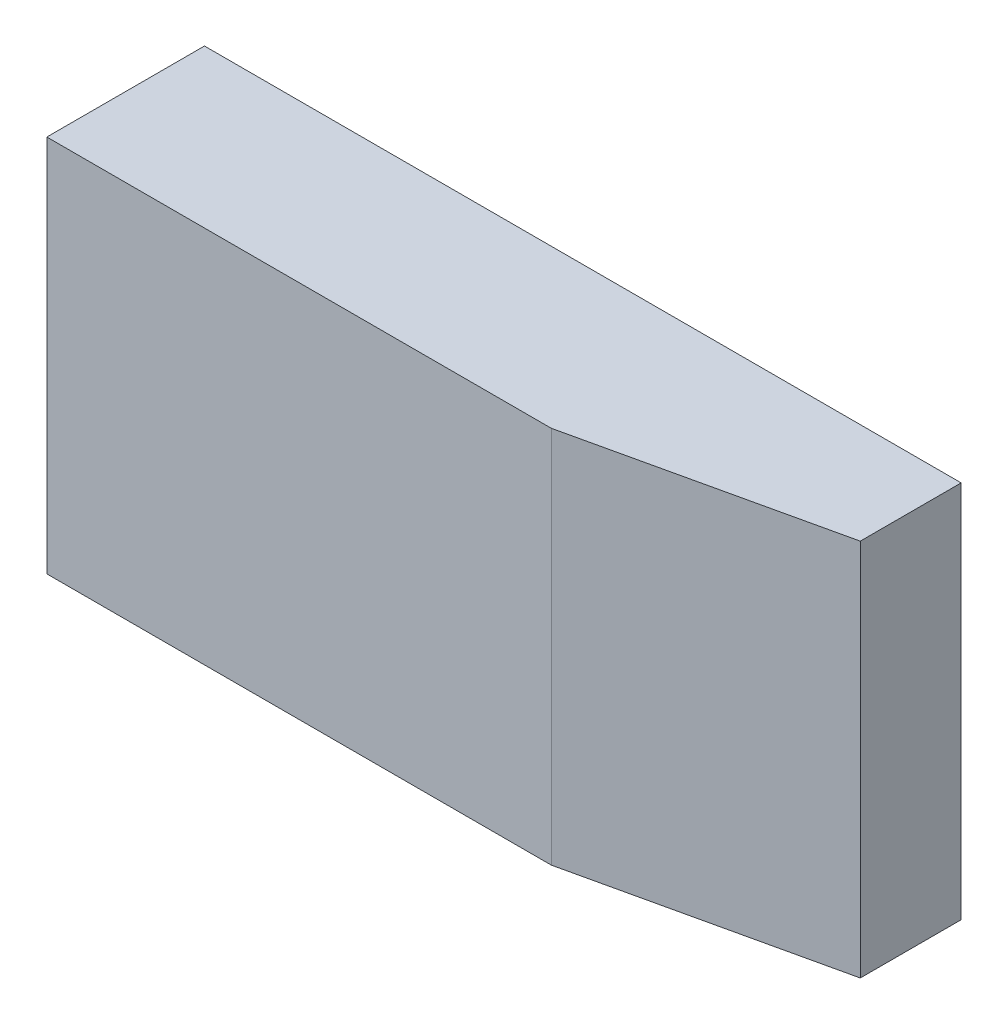
SolidWorks part; units mm, degrees
material "6061 Alloy"
ref_plane "Front Plane" through (0, 0, 0) normal (1, 0, 0) x (0, 1, 0)
ref_plane "Top Plane" through (0, 0, 0) normal (0, 0, 1) x (0, 1, 0)
ref_plane "Right Plane" through (0, 0, 0) normal (0, 1, 0) x (-1, 0, 0)
sketch "Sketch1" plane through (0, 0, 0) normal (0, 1, 0) x (-1, 0, 0)
  line L0 (0, 0) -> (0, 8)
  line L1 (0, 8) -> (20, 12.5)
  line L2 (20, 12.5) -> (60, 12.5)
  line L3 (60, 12.5) -> (60, 0)
  line L4 (60, 0) -> (0, 0)
  dimension "D1" = 60
  dimension "D2" = 40
  dimension "D3" = 8
  dimension "D4" = 12.5
extrude "Boss-Extrude1" add sketch "Sketch1" along normal blind 30
